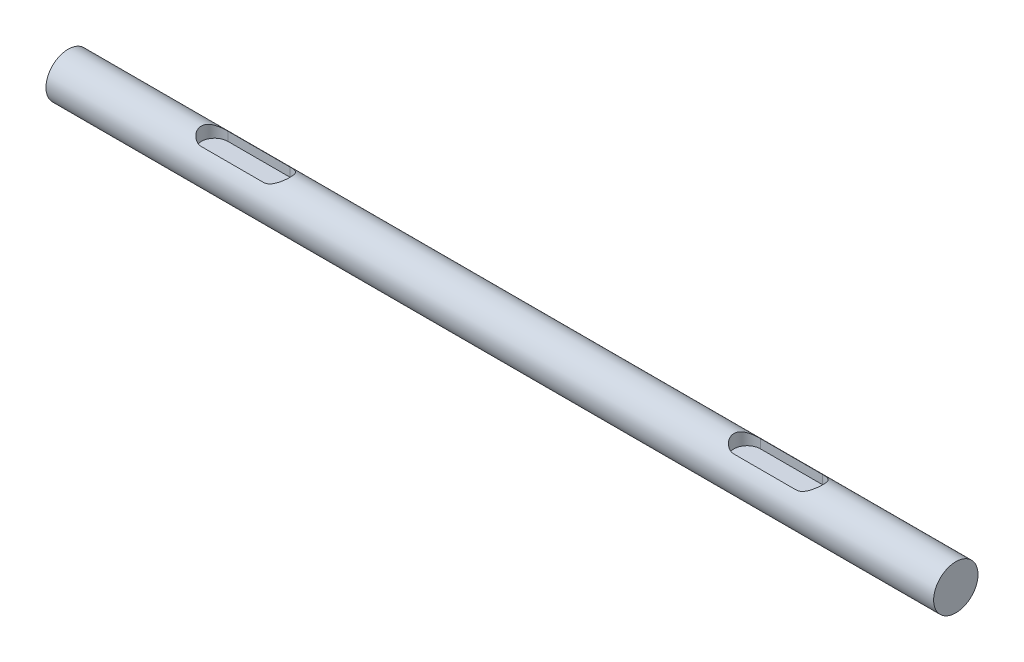
SolidWorks part; units mm, degrees
material "45"
ref_plane "前视基准面" through (0, 0, 0) normal (0, 0, 1) x (1, 0, 0)
ref_plane "上视基准面" through (0, 0, 0) normal (0, 1, 0) x (1, 0, 0)
ref_plane "右视基准面" through (0, 0, 0) normal (1, 0, 0) x (0, 0, -1)
ref_axis "基准轴1" through (88.99, 0, 0) along (-1, 0, 0)
sketch "草图1" plane through (0, 0, 0) normal (1, 0, 0) x (0, 0, -1)
  circle A0 centre (0, 0) radius 5
extrude "凸台-拉伸1" add sketch "草图1" along normal blind 100
ref_plane "基准面1" through (0, 5, 0) normal (0, 1, 0) x (1, 0, 0)
sketch "草图2" plane through (0, 5, 0) normal (0, 1, 0) x (1, 0, 0)
  line L0 (33, 3) -> (47, 3)
  line L1 (33, -3) -> (47, -3)
  arc A0 (33, 3) -> (33, -3) centre (33, 0) ccw
  arc A1 (47, 3) -> (47, -3) centre (47, 0) cw
  dimension "D1" = 3
  dimension "D2" = 14
extrude "切除-拉伸1" cut sketch "草图2" against normal blind 3
sketch "草图3" plane through (100, 0, 0) normal (1, 0, 0) x (0, 0, -1)
  circle A0 centre (0, 0) radius 5
extrude "凸台-拉伸2" add sketch "草图3" along normal blind 100
ref_plane "基准面2" through (0, 5, 0) normal (0, 1, 0) x (1, 0, 0)
sketch "草图4" plane through (0, 5, 0) normal (0, 1, 0) x (1, 0, 0)
  line L0 (153, 3) -> (167, 3)
  line L1 (153, -3) -> (167, -3)
  arc A0 (153, 3) -> (153, -3) centre (153, 0) ccw
  arc A1 (167, 3) -> (167, -3) centre (167, 0) cw
  dimension "D1" = 3
  dimension "D2" = 14
extrude "切除-拉伸2" cut sketch "草图4" against normal blind 3
